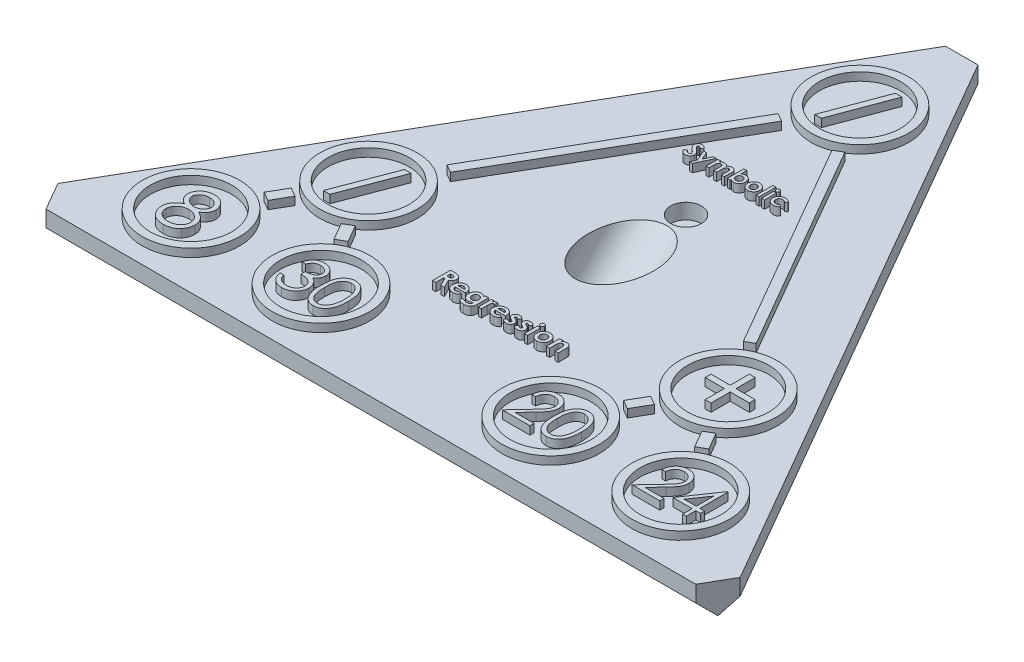
SolidWorks part; units mm, degrees
ref_plane "Front Plane" through (0, 0, 0) normal (0, 0, 1) x (1, 0, 0)
ref_plane "Top Plane" through (0, 0, 0) normal (0, 1, 0) x (1, 0, 0)
ref_plane "Right Plane" through (0, 0, 0) normal (1, 0, 0) x (0, 0, -1)
sketch "Sketch2" plane through (0, 0, 0) normal (0, 1, 0) x (1, 0, 0)
  line L0 (3.175, 75.1566) -> (-3.175, 75.1566)
  line L1 (-3.175, 75.1566) -> (-66.675, -34.8287)
  line L2 (-63.5, -40.3279) -> (63.5, -40.3279)
  line L3 (66.675, -34.8287) -> (3.175, 75.1566)
  line L4 (63.5, -40.3279) -> (66.675, -34.8287)
  line L5 (-66.675, -34.8287) -> (-63.5, -40.3279)
  circle A0 centre (0, 0) radius 40.3279 construction
  point P2 (0, 80.6558)
  point P3 (-69.85, -40.3279)
  point P4 (69.85, -40.3279)
  dimension "D1" = 139.7
extrude "Boss-Extrude1" add sketch "Sketch2" against normal blind 3.175
sketch "Sketch3" plane through (0, 0, 0) normal (0, 1, 0) x (1, 0, 0)
  line L0 (0, 55.2558) -> (0, 29.8558) construction
  line L1 (-15.4161, 29.8558) -> (15.4161, 29.8558) construction
  line L2 (0, 29.8558) -> (0, -16.2198) construction
  line L3 (-18.6015, -16.2198) -> (18.6015, -16.2198) construction
  line L5 (-47.853, -27.6279) -> (-35.153, -5.6309) construction
  line L6 (-35.153, -5.6309) -> (-22.453, -27.6279) construction
  line L7 (-22.453, -27.6279) -> (-47.853, -27.6279) construction
  line L8 (35.153, -5.6309) -> (22.453, -27.6279) construction
  line L9 (22.453, -27.6279) -> (47.853, -27.6279) construction
  line L10 (47.853, -27.6279) -> (35.153, -5.6309) construction
  line L11 (-63.5, -40.3279) -> (63.5, -40.3279) construction
  line L13 (-3.175, 75.1566) -> (-66.675, -34.8287) construction
  line L14 (66.675, -34.8287) -> (3.175, 75.1566) construction
  line L15 (0, 55.2558) -> (0, 50.9403) construction
  line L16 (-35.153, -5.6309) -> (-35.153, -9.9464) construction
  line L17 (-47.853, -27.6279) -> (-47.853, -32.7771) construction
  line L18 (-22.453, -27.6279) -> (-22.453, -31.9435) construction
  line L19 (35.153, -5.6309) -> (35.153, -11.6942) construction
  line L20 (22.453, -27.6279) -> (22.453, -31.3004) construction
  line L21 (47.853, -27.6279) -> (47.853, -31.3004) construction
  line L22 (-6.6618, 50.9403) -> (6.6618, 50.9403) construction
  line L23 (-41.8148, -9.9464) -> (-28.4911, -9.9464) construction
  line L24 (-53.8936, -32.7771) -> (-41.8123, -32.7771) construction
  line L25 (-29.1148, -31.9435) -> (-15.7911, -31.9435) construction
  line L26 (30.0305, -11.6942) -> (40.2754, -11.6942) construction
  line L27 (15.4161, -31.3004) -> (29.4898, -31.3004) construction
  line L28 (40.8161, -31.3004) -> (54.8898, -31.3004) construction
  circle A0 centre (0, 55.2558) radius 9.525 construction
  circle A1 centre (-47.853, -27.6279) radius 9.525 construction
  circle A2 centre (-22.453, -27.6279) radius 9.525 construction
  circle A3 centre (22.453, -27.6279) radius 9.525 construction
  circle A4 centre (47.853, -27.6279) radius 9.525 construction
  circle A5 centre (-35.153, -5.6309) radius 9.525 construction
  circle A6 centre (35.153, -5.6309) radius 9.525 construction
  circle A7 centre (0, 55.2558) radius 7.9375 construction
  circle A8 centre (-35.153, -5.6309) radius 7.9375 construction
  circle A9 centre (35.153, -5.6309) radius 7.9375 construction
  circle A10 centre (-47.853, -27.6279) radius 7.9375 construction
  circle A11 centre (-22.453, -27.6279) radius 7.9375 construction
  circle A12 centre (22.453, -27.6279) radius 7.9375 construction
  circle A13 centre (47.853, -27.6279) radius 7.9375 construction
  text T0 "/" font "Century Gothic" height 9.525
  text T1 "/" font "Century Gothic" height 9.525
  text T2 "8" font "Century Gothic" height 9.525
  text T3 "30" font "Century Gothic" height 7.9375
  text T4 "+" font "Century Gothic" height 12.7
  text T5 "20\r\n" font "Century Gothic" height 7.9375
  text T6 "24\r\n" font "Century Gothic" height 7.9375
  text T7 "Symbolic" font "Century Gothic" height 3.175
  text T8 "<b>Regression</b>"
  point P36 (0, 50.9403)
  point P41 (-35.153, -9.9464)
  point P43 (-47.853, -32.7771)
  point P46 (-22.453, -31.9435)
  point P51 (35.153, -11.6942)
  point P54 (22.453, -31.3004)
  point P57 (47.853, -31.3004)
  point P62 (0, 29.8558)
  point P63 (0, 29.8558)
  point P64 (0, 29.8558)
  point P70 (0, -16.2198)
  dimension "D1" = 19.05
  dimension "D2" = 1.5875
  dimension "D3" = 25.4
  dimension "D4" = 12.7
  dimension "D5" = 12.7
  dimension "D6" = 12.7
  dimension "D7" = 12.7
  dimension "D8" = 12.7
  dimension "D9" = 12.7
  dimension "D10" = 25.4
sketch "Sketch4" plane through (0, -3.175, 0) normal (0, -1, 0) x (1, 0, 0)
  line L6 (-66.675, 34.8287) -> (-3.175, -75.1566)
  line L7 (-3.175, -75.1566) -> (3.175, -75.1566)
  line L8 (3.175, -75.1566) -> (66.675, 34.8287)
  line L9 (66.675, 34.8287) -> (63.5, 40.3279)
  line L10 (63.5, 40.3279) -> (-63.5, 40.3279)
  line L11 (-63.5, 40.3279) -> (-66.675, 34.8287)
  line L12 (-66.675, 34.8287) -> (-3.175, -75.1566)
  line L13 (-3.175, -75.1566) -> (3.175, -75.1566)
  line L14 (3.175, -75.1566) -> (66.675, 34.8287)
  line L15 (66.675, 34.8287) -> (63.5, 40.3279)
  line L16 (63.5, 40.3279) -> (-63.5, 40.3279)
  line L17 (-63.5, 40.3279) -> (-66.675, 34.8287)
  dimension "D1" = 0
extrude "Boss-Extrude3" add sketch "Sketch4" along normal blind 12.7
chamfer "Chamfer1" distance 12.7 angle 45 3 edges at (0, -15.875, 40.3279) (34.925, -15.875, -20.164) (-34.925, -15.875, -20.164)
extrude "Boss-Extrude4" add sketch "Sketch3" along normal blind 1.5875
sketch "Sketch9" plane through (0, 0, 0) normal (0, 1, 0) x (1, 0, 0)
  line L0 (-35.153, -5.6309) -> (0, 55.2558) construction
  line L1 (0, 55.2558) -> (35.153, -5.6309) construction
  line L5 (-47.853, -27.6279) -> (-35.153, -5.6309) construction
  line L6 (-35.153, -5.6309) -> (-22.453, -27.6279) construction
  line L7 (-22.453, -27.6279) -> (-47.853, -27.6279) construction
  line L8 (35.153, -5.6309) -> (22.453, -27.6279) construction
  line L9 (22.453, -27.6279) -> (47.853, -27.6279) construction
  line L10 (47.853, -27.6279) -> (35.153, -5.6309) construction
  line L12 (-4.9337, 44.8646) -> (-6.5323, 45.7875)
  line L13 (-4.9337, 44.8646) -> (-28.6207, 3.8375)
  line L15 (0, 55.2558) -> (0, 50.9403) construction
  line L16 (-35.153, -5.6309) -> (-35.153, -9.9464) construction
  line L17 (-47.853, -27.6279) -> (-47.853, -32.7771) construction
  line L18 (-22.453, -27.6279) -> (-22.453, -31.9435) construction
  line L19 (35.153, -5.6309) -> (35.153, -11.6942) construction
  line L20 (22.453, -27.6279) -> (22.453, -31.3004) construction
  line L21 (47.853, -27.6279) -> (47.853, -31.3004) construction
  line L22 (-6.6618, 50.9403) -> (6.6618, 50.9403) construction
  line L23 (-41.8148, -9.9464) -> (-28.4911, -9.9464) construction
  line L24 (-53.8936, -32.7771) -> (-41.8123, -32.7771) construction
  line L25 (-29.1148, -31.9435) -> (-15.7911, -31.9435) construction
  line L26 (30.0305, -11.6942) -> (40.2754, -11.6942) construction
  line L27 (15.4161, -31.3004) -> (29.4898, -31.3004) construction
  line L28 (40.8161, -31.3004) -> (54.8898, -31.3004) construction
  line L32 (-6.5323, 45.7875) -> (-30.2193, 4.7604)
  line L33 (-28.6207, 3.8375) -> (-30.2193, 4.7604)
  line L34 (-43.4571, -17.7372) -> (-41.701, -18.751)
  line L35 (-43.4571, -17.7372) -> (-41.5207, -14.3832)
  line L36 (-41.701, -18.751) -> (-39.7646, -15.397)
  line L37 (-41.5207, -14.3832) -> (-39.7646, -15.397)
  line L38 (-43.4571, -17.7372) -> (-39.7646, -15.397) construction
  line L39 (-41.701, -18.751) -> (-41.5207, -14.3832) construction
  line L40 (-28.676, -18.877) -> (-26.92, -17.8631)
  line L41 (-28.676, -18.877) -> (-30.6125, -15.523)
  line L42 (-26.92, -17.8631) -> (-28.8564, -14.5091)
  line L43 (-30.6125, -15.523) -> (-28.8564, -14.5091)
  line L44 (-28.676, -18.877) -> (-28.8564, -14.5091) construction
  line L45 (-26.92, -17.8631) -> (-30.6125, -15.523) construction
  line L50 (-4.9337, 44.8646) -> (-30.2193, 4.7604) construction
  line L51 (-6.5323, 45.7875) -> (-28.6207, 3.8375) construction
  line L56 (0, -1.7463) -> (0, 1.7463) construction
  line L57 (28.676, -18.877) -> (26.92, -17.8631)
  line L58 (26.92, -17.8631) -> (28.8564, -14.5091)
  line L59 (30.6125, -15.523) -> (28.8564, -14.5091)
  line L60 (28.676, -18.877) -> (30.6125, -15.523)
  line L61 (43.4571, -17.7372) -> (41.701, -18.751)
  line L62 (43.4571, -17.7372) -> (41.5207, -14.3832)
  line L63 (41.5207, -14.3832) -> (39.7646, -15.397)
  line L64 (41.701, -18.751) -> (39.7646, -15.397)
  line L65 (28.6207, 3.8375) -> (30.2193, 4.7604)
  line L66 (6.5323, 45.7875) -> (30.2193, 4.7604)
  line L67 (4.9337, 44.8646) -> (6.5323, 45.7875)
  line L68 (4.9337, 44.8646) -> (28.6207, 3.8375)
  circle A0 centre (0, 55.2558) radius 9.525
  circle A1 centre (-47.853, -27.6279) radius 9.525
  circle A2 centre (-22.453, -27.6279) radius 9.525
  circle A3 centre (22.453, -27.6279) radius 9.525
  circle A4 centre (47.853, -27.6279) radius 9.525
  circle A5 centre (-35.153, -5.6309) radius 9.525
  circle A6 centre (35.153, -5.6309) radius 9.525
  circle A7 centre (0, 55.2558) radius 7.9375
  circle A8 centre (-35.153, -5.6309) radius 7.9375
  circle A9 centre (35.153, -5.6309) radius 7.9375
  circle A10 centre (-47.853, -27.6279) radius 7.9375
  circle A11 centre (-22.453, -27.6279) radius 7.9375
  circle A12 centre (22.453, -27.6279) radius 7.9375
  circle A13 centre (47.853, -27.6279) radius 7.9375
  point P22 (-17.5765, 24.8125)
  point P23 (-41.6108, -16.5671)
  point P36 (0, 50.9403)
  point P41 (-35.153, -9.9464)
  point P43 (-47.853, -32.7771)
  point P46 (-22.453, -31.9435)
  point P50 (-28.7662, -16.693)
  point P51 (35.153, -11.6942)
  point P54 (22.453, -31.3004)
  point P57 (47.853, -31.3004)
  dimension "D1" = 19.05
  dimension "D2" = 1.5875
  dimension "D3" = 25.4
extrude "Boss-Extrude5" add sketch "Sketch9" along normal blind 1.5875
sketch "Sketch10" plane through (0, -15.875, 0) normal (0, -1, 0) x (1, 0, 0)
  line L0 (0, 27.6279) -> (0, 7.3079) construction
  line L1 (47.853, 27.6279) -> (-47.853, 27.6279) construction
  dimension "D1" = 20.32
ref_plane "Plane1" through (0, -21.7515, 21.7515) normal (0, -0.7071, 0.7071) x (-1, 0, 0)
sketch "Sketch11" plane through (0, -21.7515, 21.7515) normal (0, -0.7071, 0.7071) x (-1, 0, 0)
  circle A0 centre (0, 6.0578) radius 3.9688
  circle A1 centre (0, 6.0578) radius 2.3813
  dimension "D1" = 7.9375
  dimension "D2" = 4.7625
extrude "Cut-Extrude1" cut sketch "Sketch11" against normal blind 19.05 contours A0 A1 | A1 region at (3.8565, -26.035, 17.4679)
extrude "Cut-Extrude2" cut sketch "Sketch11<3>" against normal through all contours A1 region at (0, -26.035, 17.4679)
sketch "Sketch11<3>" plane through (0, -21.7515, 21.7515) normal (0, -0.7071, 0.7071) x (-1, 0, 0) same geometry as "Sketch11"
ref_plane "Plane2" through (0, 14.1696, -14.1696) normal (0, -0.7071, 0.7071) x (-1, 0, 0)
sketch "Sketch12" plane through (0, 14.1696, -14.1696) normal (0, -0.7071, 0.7071) x (-1, 0, 0)
  circle A0 centre (0, 6.0578) radius 6.35
  circle A1 centre (0, 6.0578) radius 2.3813
  circle A2 centre (0, 6.0578) radius 2.3813 construction
  circle A3 centre (0, 6.0578) radius 3.9688
  circle A4 centre (0, 6.0578) radius 3.9688 construction
  dimension "D3" = 12.7
  dimension "D1" = 0
  dimension "D2" = 0
extrude "Cut-Extrude3" cut sketch "Sketch12" along normal blind 29.21
sketch "Sketch13" plane through (0, 0, 0) normal (0, 1, 0) x (1, 0, 0)
  circle A0 centre (0, 21.2671) radius 3 construction
  circle A1 centre (0, 21.2671) radius 3
extrude "Cut-Extrude4" cut sketch "Sketch13" against normal blind 3
